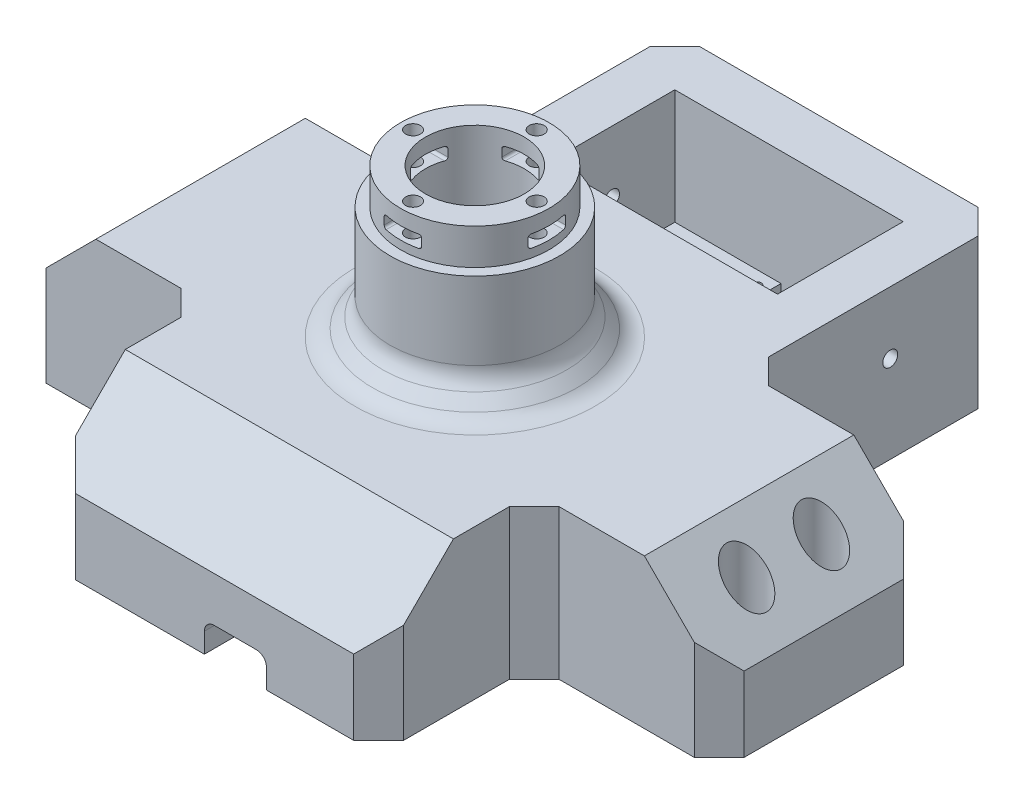
SolidWorks part; units mm, degrees
ref_plane "Front Plane" through (0, 0, 0) normal (0, 0, 1) x (1, 0, 0)
ref_plane "Top Plane" through (0, 0, 0) normal (0, 1, 0) x (1, 0, 0)
ref_plane "Right Plane" through (0, 0, 0) normal (1, 0, 0) x (0, 0, -1)
sketch "Sketch1" plane through (0, 0, 0) normal (0, 1, 0) x (1, 0, 0)
  line L0 (32.9, -22.6) -> (32.9, 22.6)
  line L1 (22.9, -12.6) -> (-22.9, -12.6)
  line L2 (22.9, -12.6) -> (22.9, 12.6)
  line L3 (22.9, 12.6) -> (-22.9, 12.6)
  line L4 (-22.9, -12.6) -> (-22.9, 12.6)
  line L5 (22.9, -12.6) -> (-22.9, 12.6) construction
  line L6 (22.9, 12.6) -> (-22.9, -12.6) construction
  line L7 (32.9, 22.6) -> (-32.9, 22.6)
  line L8 (-32.9, -22.6) -> (-32.9, 22.6)
  line L9 (32.9, -22.6) -> (-32.9, -22.6)
  point P0 (0, 0)
  dimension "D1" = 45.8
  dimension "D2" = 25.2
  dimension "D3" = 10
extrude "Boss-Extrude1" add sketch "Sketch1" along normal blind 25
sketch "Sketch2" plane through (0, 0, 0) normal (0, -1, 0) x (1, 0, 0)
  line L1 (-32.9, 22.6) -> (32.9, 22.6)
  line L2 (-32.9, 22.6) -> (-32.9, -22.6)
  line L3 (-32.9, -22.6) -> (32.9, -22.6)
  line L4 (32.9, 22.6) -> (32.9, -22.6)
extrude "Boss-Extrude2" add sketch "Sketch2" along normal blind 5
sketch "Sketch3" plane through (0, -5, 0) normal (0, -1, 0) x (1, 0, 0)
  circle A0 centre (-3.7, 10) radius 0.75
  circle A1 centre (20.8, 10) radius 0.75
  circle A2 centre (20.8, -10) radius 0.75
  circle A3 centre (-3.7, -10) radius 0.75
  dimension "D1" = 1.5
extrude "Cut-Extrude1" cut sketch "Sketch3" against normal through all
sketch "Sketch4" plane through (0, -5, 0) normal (0, -1, 0) x (1, 0, 0)
  line L0 (-32.9, -22.6) -> (32.9, -22.6) construction
  line L2 (-1.6, -7.5) -> (-1.6, -22.6)
  line L3 (-1.6, -22.6) -> (10.4, -22.6)
  line L4 (10.4, 7.5) -> (10.4, -22.6)
  line L5 (-32.9, 22.6) -> (-32.9, -22.6) construction
  line L6 (10.4, 7.5) -> (-32.9, 7.5)
  line L8 (-1.6, -7.5) -> (-32.9, -7.5)
  line L9 (-32.9, 7.5) -> (-32.9, -7.5)
  line L10 (32.9, 0) -> (-32.9, 0) construction
  line L11 (32.9, -22.6) -> (32.9, 22.6) construction
  line L12 (32.9, 22.6) -> (32.9, -22.6) construction
  dimension "D1" = 15
  dimension "D2" = 12
  dimension "D3" = 22.5
extrude "Cut-Extrude2" cut sketch "Sketch4" against normal blind 5
fillet "Fillet1" radius 2 6 edges at (10.4, -2.5, 7.5) (-1.6, -2.5, -7.5) (-1.6, 0, -17.6) (10.4, 0, -17.6) (-27.9, 0, 7.5) (-27.9, 0, -7.5)
sketch "Sketch5" plane through (0, -5, 0) normal (0, -1, 0) x (1, 0, 0)
  circle A0 centre (-3.7, 10) radius 3
  circle A1 centre (20.8, 10) radius 3
  circle A2 centre (20.8, -10) radius 3
  circle A3 centre (-3.7, -10) radius 3
  dimension "D1" = 6
extrude "Cut-Extrude6" cut sketch "Sketch5" against normal blind 4
sketch "Sketch6" plane through (0, 0, 22.6) normal (0, 0, 1) x (1, 0, 0)
  line L1 (-32.9, 25) -> (32.9, 25)
  line L2 (-32.9, 25) -> (-32.9, -5)
  line L3 (-32.9, -5) -> (32.9, -5)
  line L4 (32.9, 25) -> (32.9, -5)
extrude "Boss-Extrude3" add sketch "Sketch6" along normal blind 80
sketch "Sketch7" plane through (0, 25, 0) normal (0, 1, 0) x (1, 0, 0)
  line L2 (32.9, -102.6) -> (32.9, 22.6) construction
  line L3 (32.9, 22.6) -> (-32.9, 22.6) construction
  circle A0 centre (0, -50.4) radius 9.9
  circle A1 centre (0, -50.4) radius 14.9
  circle A2 centre (0, -50.4) radius 2.0648 construction
  dimension "D1" = 29.8
  dimension "D2" = 5
  dimension "D3" = 4.1296
  dimension "D4" = 32.9
  dimension "D5" = 73
extrude "Boss-Extrude4" add sketch "Sketch7" along normal blind 29.8
sketch "Sketch8" plane through (0, 25, 0) normal (0, 1, 0) x (1, 0, 0)
  circle A0 centre (0, -50.4) radius 17
  circle A1 centre (0, -50.4) radius 14.9
  circle A2 centre (0, -50.4) radius 14.9 construction
  dimension "D1" = 34
extrude "Boss-Extrude5" add sketch "Sketch8" along normal blind 22.6
sketch "Sketch9" plane through (0, 25, 0) normal (0, 1, 0) x (1, 0, 0)
  line L1 (70, -71.4) -> (-70, -71.4)
  line L2 (70, -71.4) -> (70, -29.4)
  line L3 (70, -29.4) -> (-70, -29.4)
  line L4 (-70, -71.4) -> (-70, -29.4)
  line L5 (70, -71.4) -> (-70, -29.4) construction
  line L6 (70, -29.4) -> (-70, -71.4) construction
  point P0 (0, -50.4)
  dimension "D1" = 42
  dimension "D2" = 140
extrude "Boss-Extrude6" add sketch "Sketch9" against normal up to surface (30 mm away) up to face at (-15.3822, -5, -14.8818)
sketch "Sketch10" plane through (0, -5, 0) normal (0, -1, 0) x (1, 0, 0)
  line L0 (8.4, 7.5) -> (-2.0417, 7.5) construction
  line L1 (-2.0417, 7.5) -> (8.4, 7.5)
  line L2 (-2.0417, 7.5) -> (-2.0417, 102.6)
  line L3 (-2.0417, 102.6) -> (10.4, 102.6)
  line L4 (10.4, 5.5) -> (10.4, 102.6)
  line L5 (-32.9, 102.6) -> (32.9, 102.6) construction
  line L6 (10.4, -12.6) -> (10.4, -22.6) construction
  arc A0 (-2.0417, 7.5) -> (-5.3583, 7.5) centre (-3.7, 10) ccw construction
  arc A1 (10.4, 5.5) -> (8.4, 7.5) centre (8.4, 5.5) ccw construction
  arc A2 (10.4, 5.5) -> (8.4, 7.5) centre (8.4, 5.5) ccw
extrude "Cut-Extrude7" cut sketch "Sketch10" against normal blind 6
fillet "Fillet2" radius 2 2 edges at (10.4, 1, 57.6) (-2.0417, 1, 57.6)
sketch "Sketch11" plane through (0, 25, 0) normal (0, 1, 0) x (1, 0, 0)
  circle A0 centre (0, -50.4) radius 9.9
  circle A1 centre (0, -50.4) radius 9.9 construction
extrude "Cut-Extrude8" cut sketch "Sketch11" against normal through all
chamfer "Chamfer1" distance 5 angle 45 1 edges at (0, 25, 33.4)
fillet "Fillet3" radius 5 2 edges at (0, 25, 28.4) (0, 30, 33.4)
chamfer "Chamfer2" distance 15 angle 45 3 edges at (70, 25, 50.4) (0, 25, 102.6) (-70, 25, 50.4)
chamfer "Chamfer3" distance 5 angle 45 12 edges at (32.9, 10, -22.6) (32.9, 10, 29.4) (70, 2.5, 29.4) (70, 2.5, 71.4) (32.9, 10, 71.4) (32.9, 2.5, 102.6) (-32.9, 2.5, 102.6) (-32.9, 10, 71.4) (-70, 2.5, 71.4) (-70, 2.5, 29.4) (-32.9, 10, 29.4) (-32.9, 10, -22.6)
sketch "Sketch13" plane through (0, 54.8, 0) normal (0, 1, 0) x (1, 0, 0)
  circle A0 centre (0, -50.4) radius 12.4 construction
  circle A2 centre (0, -38) radius 1.5
  circle A3 centre (12.4, -50.4) radius 1.5
  circle A4 centre (0, -62.8) radius 1.5
  circle A5 centre (-12.4, -50.4) radius 1.5
  point P14 (0, -50.4)
  dimension "D1" = 24.8
  dimension "D2" = 3
  dimension "D3" = 4
extrude "Cut-Extrude9" cut sketch "Sketch13" against normal through all
sketch "Sketch14" plane through (0, -5, 0) normal (0, -1, 0) x (1, 0, 0)
  line L0 (-70, 50.4) -> (70, 50.4) construction
  line L1 (-70, 34.4) -> (-70, 66.4) construction
  line L2 (70, 66.4) -> (70, 34.4) construction
  line L3 (70, 34.4) -> (70, 66.4) construction
  line L4 (62, 42.9) -> (-62, 42.9) construction
  line L5 (62, 42.9) -> (62, 57.9) construction
  line L6 (62, 57.9) -> (-62, 57.9) construction
  line L7 (-62, 42.9) -> (-62, 57.9) construction
  line L8 (62, 42.9) -> (-62, 57.9) construction
  line L9 (62, 57.9) -> (-62, 42.9) construction
  circle A0 centre (-62, 57.9) radius 1.75
  circle A1 centre (62, 57.9) radius 1.75
  circle A2 centre (62, 42.9) radius 1.75
  circle A3 centre (-62, 42.9) radius 1.75
  point P6 (0, 50.4)
  dimension "D3" = 3.5
  dimension "D1" = 8
  dimension "D2" = 15
extrude "Cut-Extrude10" cut sketch "Sketch14" against normal through all
sketch "Sketch15" plane through (0, -5, 0) normal (0, -1, 0) x (1, 0, 0)
  circle A0 centre (-62, 57.9) radius 4
  circle A1 centre (-62, 42.9) radius 4
  circle A2 centre (62, 57.9) radius 4
  circle A3 centre (62, 42.9) radius 4
  dimension "D1" = 8
extrude "Cut-Extrude11" cut sketch "Sketch15" against normal through all from offset 3 offset against normal yes
sketch "Sketch16" plane through (32.9, 0, 0) normal (1, 0, 0) x (0, 0, -1)
  line L0 (0, 0) -> (0, 25) construction
  line L1 (-24.4, 25) -> (17.6, 25) construction
  circle A0 centre (0, 12.5) radius 1.5
  dimension "D1" = 3
extrude "Cut-Extrude12" cut sketch "Sketch16" against normal through all
sketch "Sketch17" plane through (0, 0, 0) normal (0, 1, 0) x (1, 0, 0)
  line L0 (22.9, 12.6) -> (10.1321, 12.6) construction
  line L1 (18.4, 12.6) -> (22.9, 12.6)
  line L2 (18.4, 12.6) -> (18.4, 2.6)
  line L3 (18.4, 2.6) -> (22.9, 2.6)
  line L4 (-22.9, 7.5) -> (-3.6, 7.5)
  line L5 (-1.6, 9.5) -> (-1.6, 12.6)
  line L7 (-22.9, 12.6) -> (-22.9, 7.5)
  line L8 (-22.9, 7.5) -> (-3.6, 7.5)
  line L11 (-22.9, 12.6) -> (-22.9, 7.5)
  line L12 (-22.9, -12.6) -> (-1.7737, -12.6)
  line L14 (-1.7737, -7.5) -> (-22.9, -7.5)
  line L15 (-22.9, -7.5) -> (-22.9, -12.6)
  line L16 (-22.9, -12.6) -> (-1.7737, -12.6)
  line L18 (-1.7737, -7.5) -> (-22.9, -7.5)
  line L19 (-22.9, -7.5) -> (-22.9, -12.6)
  line L20 (22.9, 12.6) -> (22.9, 2.6)
  line L21 (22.9, -12.6) -> (22.9, 12.6) construction
  line L22 (-22.9, -12.6) -> (22.9, -12.6) construction
  line L23 (22.9, -2.6) -> (18.4, -2.6)
  line L24 (22.9, -2.6) -> (22.9, -12.6)
  line L25 (22.9, -12.6) -> (18.4, -12.6)
  line L26 (18.4, -2.6) -> (18.4, -12.6)
  line L30 (-1.6, 9.5) -> (-1.6, 12.6)
  line L31 (-1.6, 12.6) -> (-22.9, 12.6)
  line L32 (-1.6, 12.6) -> (-22.9, 12.6)
  line L33 (-1.7737, -12.6) -> (-1.7737, -7.5)
  line L34 (-1.7737, -12.6) -> (-1.7737, -7.5)
  circle A0 centre (-3.7, -10) radius 0.75 construction
  arc A1 (-3.6, 7.5) -> (-1.6, 9.5) centre (-3.6, 9.5) ccw
  circle A3 centre (-3.7, -10) radius 0.75
  circle A4 centre (-3.7, 10) radius 0.75 construction
  circle A5 centre (-3.7, 10) radius 0.75
  circle A6 centre (20.8, -10) radius 0.75 construction
  circle A7 centre (20.8, -10) radius 0.75
  circle A8 centre (20.8, 10) radius 0.75 construction
  circle A9 centre (20.8, 10) radius 0.75
  arc A14 (-3.6, 7.5) -> (-1.6, 9.5) centre (-3.6, 9.5) ccw
  dimension "D3" = 10
  dimension "D4" = 4.5
  dimension "D1" = 0
  dimension "D2" = 0
extrude "Boss-Extrude7" add sketch "Sketch17" along normal blind 2
sketch "Sketch18" plane through (0, 54.8, 0) normal (0, 1, 0) x (1, 0, 0)
  line L0 (0, -35.9796) -> (0, -64.8204) construction
  line L1 (-3.75, -35.9796) -> (3.75, -35.9796) construction
  line L2 (-3.75, -35.9796) -> (-3.75, -41.2377)
  line L3 (-3.75, -64.8204) -> (3.75, -64.8204) construction
  line L4 (3.75, -35.9796) -> (3.75, -41.2377)
  line L5 (14.4204, -46.65) -> (9.1623, -46.65)
  line L6 (14.4204, -46.65) -> (14.4204, -54.15) construction
  line L7 (14.4204, -54.15) -> (9.1623, -54.15)
  line L8 (-14.4204, -46.65) -> (-14.4204, -54.15) construction
  line L9 (14.4204, -50.4) -> (-14.4204, -50.4) construction
  line L10 (-9.1623, -46.65) -> (-14.4204, -46.65)
  line L11 (-9.1623, -54.15) -> (-14.4204, -54.15)
  line L12 (3.75, -46.65) -> (-3.75, -46.65) construction
  line L13 (3.75, -54.15) -> (-3.75, -54.15) construction
  line L14 (3.75, -59.5623) -> (3.75, -64.8204)
  line L15 (-3.75, -59.5623) -> (-3.75, -64.8204)
  line L16 (3.75, -46.65) -> (3.75, -54.15) construction
  line L17 (-3.75, -46.65) -> (-3.75, -54.15) construction
  circle A0 centre (0, -50.4) radius 14.9 construction
  circle A1 centre (0, -50.4) radius 14.9 construction
  circle A4 centre (0, -50.4) radius 9.9 construction
  arc A5 (-3.75, -59.5623) -> (3.75, -59.5623) centre (0, -50.4) ccw
  arc A6 (-3.75, -64.8204) -> (3.75, -64.8204) centre (0, -50.4) ccw
  arc A7 (9.1623, -54.15) -> (9.1623, -46.65) centre (0, -50.4) ccw
  arc A8 (14.4204, -54.15) -> (14.4204, -46.65) centre (0, -50.4) ccw
  arc A9 (3.75, -35.9796) -> (-3.75, -35.9796) centre (0, -50.4) ccw
  arc A10 (3.75, -41.2377) -> (-3.75, -41.2377) centre (0, -50.4) ccw
  arc A11 (-9.1623, -46.65) -> (-9.1623, -54.15) centre (0, -50.4) ccw
  arc A12 (-14.4204, -46.65) -> (-14.4204, -54.15) centre (0, -50.4) ccw
  point P20 (0, -50.4)
  dimension "D1" = 7.5
extrude "Cut-Extrude13" cut sketch "Sketch18" against normal blind 2.5 from offset 3 offset against normal yes
fillet "Fillet4" radius 0.5 16 edges at (-3.75, 51.8, 38.6087) (-3.75, 49.3, 38.6087) (3.75, 49.3, 38.6087) (3.75, 51.8, 38.6087) (11.7913, 51.8, 46.65) (11.7913, 49.3, 46.65) (11.7913, 49.3, 54.15) (11.7913, 51.8, 54.15) (3.75, 51.8, 62.1913) (3.75, 49.3, 62.1913) (-3.75, 49.3, 62.1913) (-3.75, 51.8, 62.1913) (-11.7913, 51.8, 54.15) (-11.7913, 49.3, 54.15) (-11.7913, 49.3, 46.65) (-11.7913, 51.8, 46.65)
